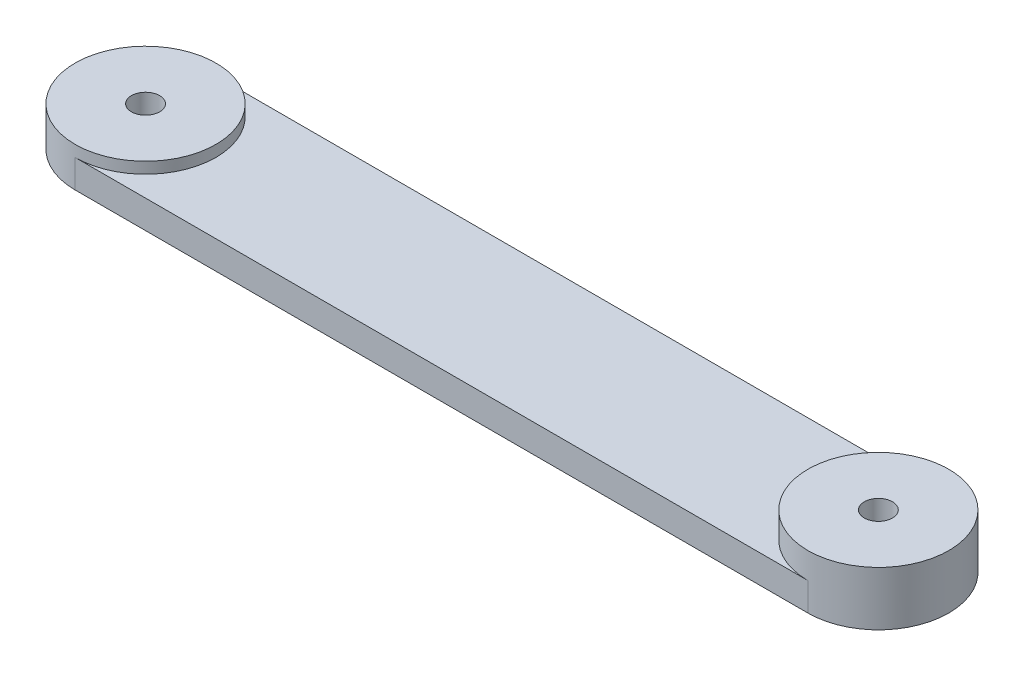
SolidWorks part; units mm, degrees
ref_plane "前视基准面" through (0, 0, 0) normal (0, 0, 1) x (1, 0, 0)
ref_plane "上视基准面" through (0, 0, 0) normal (0, 1, 0) x (1, 0, 0)
ref_plane "右视基准面" through (0, 0, 0) normal (1, 0, 0) x (0, 0, -1)
sketch "草图1" plane through (0, 0, 0) normal (0, 1, 0) x (1, 0, 0)
  line L0 (-65, 0) -> (65, 0) construction
  line L1 (-65, 12.5) -> (65, 12.5)
  line L2 (-65, -12.5) -> (65, -12.5)
  arc A0 (-65, 12.5) -> (-65, -12.5) centre (-65, 0) ccw
  arc A1 (65, -12.5) -> (65, 12.5) centre (65, 0) ccw
  point P2 (0, 0)
  dimension "D2" = 12.5
  dimension "D1" = 130
extrude "凸台-拉伸1" add sketch "草图1" along normal blind 5
sketch "草图5" plane through (0, 5, 0) normal (0, 1, 0) x (1, 0, 0)
  circle A0 centre (-65, 0) radius 12.5
  arc A1 (-65, 12.5) -> (-65, -12.5) centre (-65, 0) ccw construction
extrude "凸台-拉伸2" add sketch "草图5" along normal blind 2
sketch "草图6" plane through (0, 7, 0) normal (0, 1, 0) x (1, 0, 0)
  circle A0 centre (-65, 0) radius 2.5
  dimension "D1" = 5
extrude "切除-拉伸1" cut sketch "草图6" against normal up to next
sketch "草图8" plane through (0, 5, 0) normal (0, 1, 0) x (1, 0, 0)
  circle A0 centre (65, 0) radius 12.5
  arc A1 (65, -12.5) -> (65, 12.5) centre (65, 0) ccw construction
extrude "凸台-拉伸3" add sketch "草图8" along normal blind 4.6
sketch "草图7" plane through (0, 9.6, 0) normal (0, 1, 0) x (1, 0, 0)
  circle A0 centre (65, 0) radius 2.5
  dimension "D1" = 5
extrude "切除-拉伸2" cut sketch "草图7" against normal up to next
